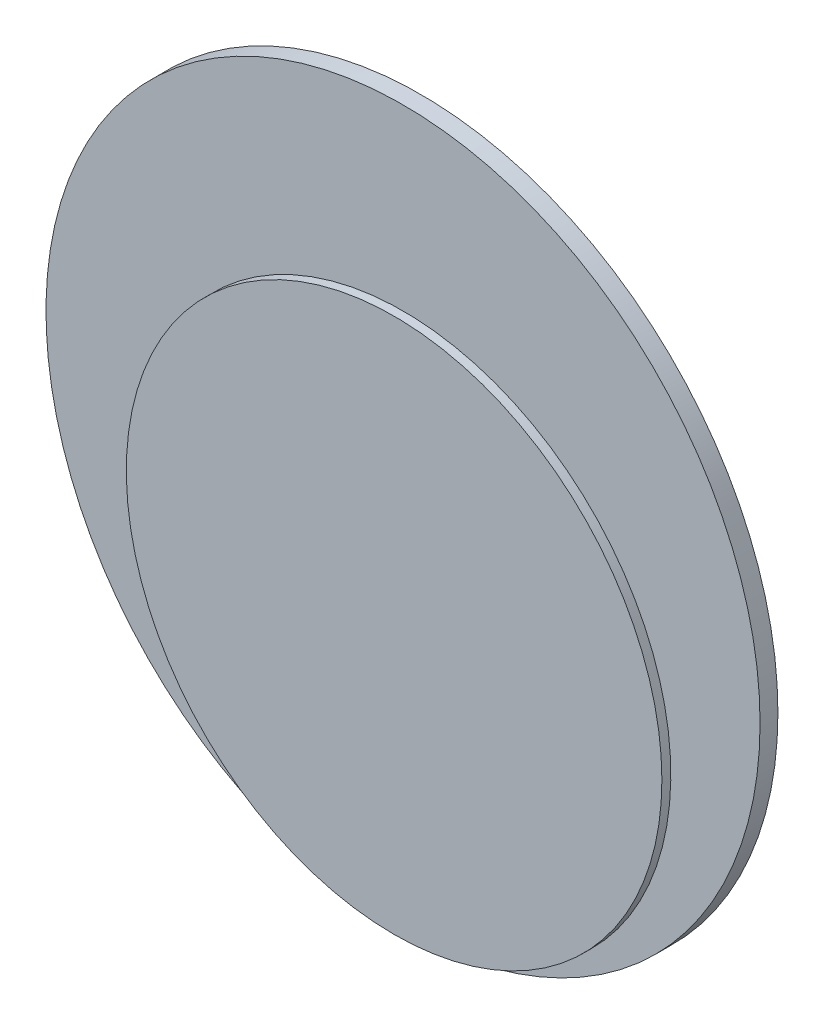
SolidWorks part; units mm, degrees
material "ABS"
ref_plane "Front Plane" through (0, 0, 0) normal (0, 0, 1) x (1, 0, 0)
ref_plane "Top Plane" through (0, 0, 0) normal (0, 1, 0) x (1, 0, 0)
ref_plane "Right Plane" through (0, 0, 0) normal (1, 0, 0) x (0, 0, -1)
sketch "Sketch1" plane through (0, 0, 0) normal (0, 0, 1) x (1, 0, 0)
  circle A0 centre (0, 0) radius 20
  circle A1 centre (0, -5) radius 15
  dimension "D1" = 40
  dimension "D2" = 30
extrude "Boss-Extrude1" add sketch "Sketch1" against normal blind 1 contours A0
extrude "Boss-Extrude2" add sketch "Sketch1<3>" along normal blind 0.5 contours A1
sketch "Sketch1<3>" plane through (0, 0, 0) normal (0, 0, 1) x (1, 0, 0) same geometry as "Sketch1"
